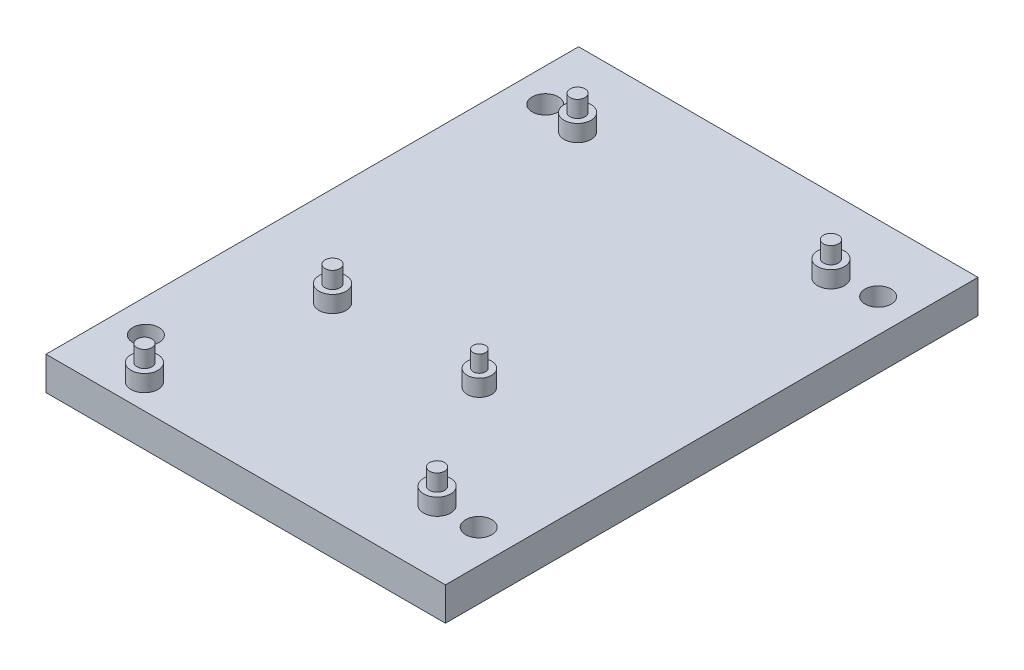
SolidWorks part; units mm, degrees
ref_plane "Front Plane" through (0, 0, 0) normal (0, 0, 1) x (1, 0, 0)
ref_plane "Top Plane" through (0, 0, 0) normal (0, 1, 0) x (1, 0, 0)
ref_plane "Right Plane" through (0, 0, 0) normal (1, 0, 0) x (0, 0, -1)
sketch "Sketch1" plane through (0, 0, 0) normal (0, 1, 0) x (1, 0, 0)
  line L1 (-38.1, -50.8) -> (38.1, -50.8)
  line L2 (-38.1, -50.8) -> (-38.1, 50.8)
  line L3 (-38.1, 50.8) -> (38.1, 50.8)
  line L4 (38.1, -50.8) -> (38.1, 50.8)
  line L5 (-38.1, -50.8) -> (38.1, 50.8) construction
  line L6 (-38.1, 50.8) -> (38.1, -50.8) construction
  circle A0 centre (-31.75, 38.1) radius 2.5
  circle A1 centre (-31.75, -38.1) radius 2.5
  circle A2 centre (31.75, 38.1) radius 2.5
  circle A3 centre (31.75, -38.1) radius 2.5
  point P0 (0, 0)
  point P14 (0, 0)
  point P15 (0, 0)
  point P16 (0, 0)
  point P17 (0, 0)
  dimension "D3" = 5
  dimension "D1" = 76.2
  dimension "D2" = 101.6
  dimension "D4" = 6.35
  dimension "D5" = 6.35
  dimension "D6" = 12.7
  dimension "D7" = 12.7
extrude "Boss-Extrude1" add sketch "Sketch1" along normal blind 6.35
sketch "Sketch2" plane through (0, 6.35, 0) normal (0, 1, 0) x (1, 0, 0)
  circle A0 centre (-24.1681, -45.9486) radius 1.5621 construction
  circle A1 centre (24.1681, -38.4556) radius 1.5621 construction
  circle A2 centre (-19.2896, -14.9479) radius 1.5621 construction
  circle A3 centre (8.7266, -14.9479) radius 1.3153 construction
  circle A4 centre (-24.1681, 36.6776) radius 1.5621 construction
  circle A5 centre (24.1681, 36.6776) radius 1.5621 construction
  circle A6 centre (-24.1681, -45.9486) radius 1.5621 construction
  circle A7 centre (24.1681, -38.4556) radius 1.5621 construction
  circle A8 centre (-19.2896, -14.9479) radius 1.5621 construction
  circle A9 centre (8.7266, -14.9479) radius 1.3153 construction
  circle A10 centre (-24.1681, 36.6776) radius 1.5621 construction
  circle A11 centre (24.1681, 36.6776) radius 1.5621 construction
  circle A12 centre (-24.1681, 36.6776) radius 2.5781
  circle A13 centre (24.1681, 36.6776) radius 2.5781
  circle A14 centre (-19.2896, -14.9479) radius 2.5781
  circle A15 centre (24.1681, -38.4556) radius 2.5781
  circle A16 centre (-24.1681, -45.9486) radius 2.5781
  circle A17 centre (-24.1681, 36.6776) radius 1.4351
  circle A18 centre (24.1681, 36.6776) radius 1.4351
  circle A19 centre (-19.2896, -14.9479) radius 1.4351
  circle A20 centre (-24.1681, -45.9486) radius 1.4351
  circle A21 centre (24.1681, -38.4556) radius 1.4351
  circle A22 centre (8.7266, -14.9479) radius 1.1883
  circle A23 centre (8.7266, -14.9479) radius 2.3313
  dimension "D1" = 1.016
  dimension "D2" = 0.127
  dimension "D3" = 0.127
  dimension "D4" = 1.016
extrude "Boss-Extrude2" add sketch "Sketch2" along normal blind 3.175 contours A17 | A12 A17 | A18 | A13 A18 | A19 | A14 A19 | A22 | A23 A22 | A20 | A16 A20 | A21 | A15 A21 region at (-26.6733, 6.35, -36.6776) region at (21.6629, 6.35, -36.6776) region at (-21.7948, 6.35, 14.9479) region at (21.6629, 6.35, 38.4556) region at (-26.6733, 6.35, 45.9486) region at (-24.1681, 6.35, -36.6776) region at (24.1681, 6.35, -36.6776) region at (-19.2896, 6.35, 14.9479) region at (-24.1681, 6.35, 45.9486) region at (24.1681, 6.35, 38.4556) region at (8.7266, 6.35, 14.9479) region at (6.4613, 6.35, 14.9479)
extrude "Boss-Extrude3" add sketch "Sketch2<4>" along normal blind 3.175 from surface contours A17 | A18 | A19 | A22 | A21 | A20 region at (-24.1681, 6.35, -36.6776) region at (24.1681, 6.35, -36.6776) region at (-19.2896, 6.35, 14.9479) region at (-24.1681, 6.35, 45.9486) region at (24.1681, 6.35, 38.4556) region at (8.7266, 6.35, 14.9479) starting at face at (-24.1681, 9.525, -34.0995)
sketch "Sketch2<4>" plane through (0, 6.35, 0) normal (0, 1, 0) x (1, 0, 0) same geometry as "Sketch2"
